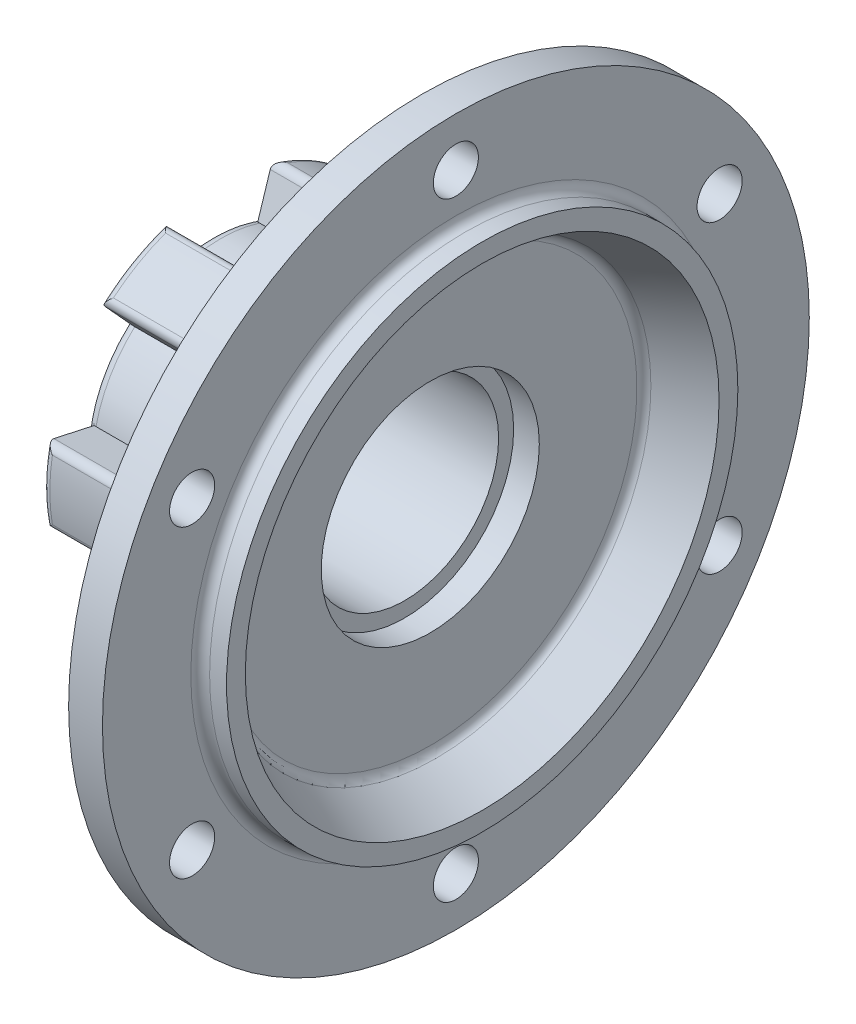
SolidWorks part; units mm, degrees
ref_plane "Front Plane" through (0, 0, 0) normal (0, 0, 1) x (1, 0, 0)
ref_plane "Top Plane" through (0, 0, 0) normal (0, 1, 0) x (1, 0, 0)
ref_plane "Right Plane" through (0, 0, 0) normal (1, 0, 0) x (0, 0, -1)
sketch "Sketch1" plane through (0, 0, 0) normal (0, 0, 1) x (1, 0, 0)
  line L0 (0, 0) -> (0, -31.5) construction
  line L1 (0, 0) -> (-93.0643, 0) construction
  line L2 (0, -31.5) -> (0, -34)
  line L3 (0, -34) -> (-3.5, -34)
  line L4 (-3.5, -34) -> (-3.5, -47)
  line L5 (-3.5, -47) -> (-8, -47)
  line L6 (-8, -47) -> (-8, -30.5)
  line L7 (-8, -30.5) -> (-13, -30.5)
  line L8 (-13, -30.5) -> (-13, -23.5)
  line L9 (-13, -23.5) -> (-35, -23.5)
  line L10 (-35, -23.5) -> (-35, -17)
  line L11 (-35, -17) -> (-36, -17)
  line L12 (-36, -17) -> (-36, -12.5)
  line L13 (-36, -12.5) -> (-10.3132, -12.5)
  line L14 (-10.3132, -12.5) -> (-10.3132, -14.5)
  line L15 (-10.3132, -14.5) -> (-6.9043, -14.5)
  line L16 (-6.9043, -14.5) -> (-6.9043, -28.2805)
  line L17 (-6.9043, -28.2805) -> (0, -31.5)
  point P10 (3.8275, -19.5826)
  point P20 (-9.0486, -18.318)
  point P21 (0, 0)
  point P22 (0, 0)
  point P23 (0, 0)
  point P24 (0, 0)
  point P25 (0, 0)
  point P26 (-10.3132, -12.5)
  dimension "D1" = 31.5
  dimension "D2" = 2.5
  dimension "D3" = 3.5
  dimension "D4" = 47
  dimension "D5" = 5
  dimension "D6" = 7
  dimension "D7" = 22
  dimension "D8" = 6.5
  dimension "D9" = 4.5
  dimension "D10" = 12.5
  dimension "D11" = 2
  dimension "D12" = 1
  dimension "D13" = 115
  dimension "D14" = 4.5
revolve "Revolve1" add sketch "Sketch1" angle 360 about L1
sketch "Sketch2" plane through (-35, 0, 0) normal (-1, 0, 0) x (0, 0, 1)
  line L0 (0, 0) -> (0, -47) construction
  line L1 (14.2427, -44.79) -> (0, 0) construction
  line L2 (0, 0) -> (-14.2427, -44.79) construction
  line L3 (-5.1516, -16.2006) -> (-9.2426, -29.0659)
  line L4 (5.1516, -16.2006) -> (9.2426, -29.0659)
  circle A0 centre (0, 0) radius 47 construction
  arc A1 (-5.1516, -16.2006) -> (5.1516, -16.2006) centre (0, 0) ccw
  circle A2 centre (0, 0) radius 17 construction
  arc A3 (9.2426, -29.0659) -> (-9.2426, -29.0659) centre (0, 0) cw
  circle A4 centre (0, 0) radius 30.5 construction
  dimension "D1" = 35.28
extrude "Cut-Extrude1" cut sketch "Sketch2" against normal blind 13
sketch "Sketch3" plane through (-8, 0, 0) normal (-1, 0, 0) x (0, 0, 1)
  circle A0 centre (0, -40.5) radius 3
  dimension "D1" = 6
  dimension "D2" = 40.5
extrude "Cut-Extrude2" cut sketch "Sketch3" against normal through all
pattern_circular "CirPattern1" count 6 over 360 about axis through (0, 0, 0) along (1, 0, 0) of "Cut-Extrude2", "Cut-Extrude1"
fillet "Fillet1" radius 1 26 edges at (-28.5, -5.0303, 22.9553) (-35, 0, 23.5) (-28.5, 5.0303, 22.9553) (-22, 11.75, 20.3516) (-28.5, 17.3648, 15.834) (-35, 20.3516, 11.75) (-28.5, 22.395, 7.1213) (-22, 23.5, 0) (-28.5, 22.395, -7.1213) (-35, 20.3516, -11.75) (-28.5, 17.3648, -15.834) (-22, 11.75, -20.3516) (-28.5, 5.0303, -22.9553) (-35, 0, -23.5) (-28.5, -5.0303, -22.9553) (-22, -11.75, -20.3516) (-28.5, -17.3648, -15.834) (-35, -20.3516, -11.75) (-28.5, -22.395, -7.1213) (-22, -23.5, 0) (-28.5, -22.395, 7.1213) (-35, -20.3516, 11.75) (-28.5, -17.3648, 15.834) (-22, -11.75, 20.3516) (-13, 0, -23.5) (-8, 0, -30.5)
fillet "Fillet2" radius 1.25 3 edges at (-3.5, 0, -34) (-6.9043, 0, -28.2805) (-36, 0, -17)
